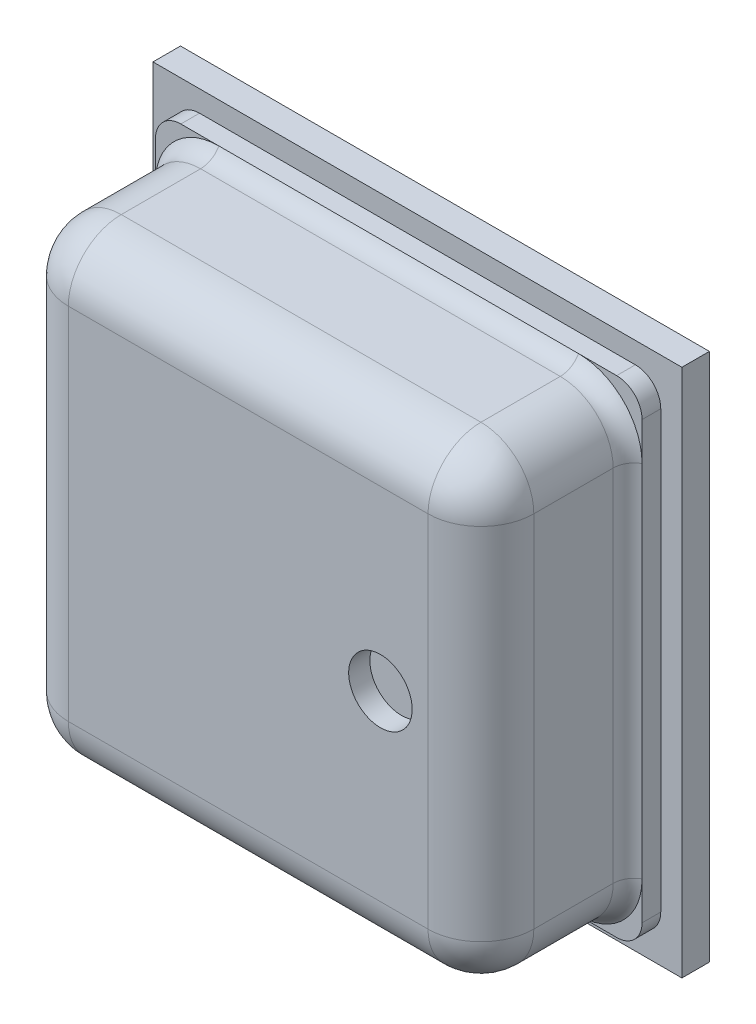
SolidWorks part; units mm, degrees
ref_plane "Спереди" through (0, 0, 0) normal (0, 0, 1) x (1, 0, 0)
ref_plane "Сверху" through (0, 0, 0) normal (0, 1, 0) x (1, 0, 0)
ref_plane "Справа" through (0, 0, 0) normal (1, 0, 0) x (0, 0, -1)
other "Configuration Table"
sketch "Эскиз1" plane through (0, 0, 0) normal (0, 1, 0) x (1, 0, 0)
  line L0 (58.2389, -66.049) -> (296.1934, -66.049) construction
  line L1 (0, 0) -> (0, -0.93) construction
  line L2 (-1.25, 0) -> (1.25, 0)
  line L3 (-1.25, 0) -> (-1.25, -0.13)
  line L4 (-1.25, -0.13) -> (1.25, -0.13)
  line L5 (1.25, 0) -> (1.25, -0.13)
  line L6 (0, -0.88) -> (-0.85, -0.88) construction
  line L7 (-1.2, -0.305) -> (-1.2, -0.155) construction
  line L8 (-1.05, -0.68) -> (-1.05, -0.305) construction
  line L9 (0, -0.83) -> (-0.85, -0.83)
  line L10 (-1, -0.68) -> (-1, -0.305)
  line L11 (0, -0.93) -> (-0.85, -0.93)
  line L12 (-1.1, -0.68) -> (-1.1, -0.305)
  line L13 (0, -0.83) -> (0, -0.93)
  line L14 (-1.2, -0.105) -> (-1.2, -0.205)
  line L15 (-1.15, -0.2184) -> (-1.15, -0.13)
  line L16 (1.15, -0.2184) -> (1.15, -0.13)
  line L17 (1.1, -0.68) -> (1.1, -0.305)
  line L18 (1, -0.68) -> (1, -0.305)
  line L19 (0, -0.93) -> (0.85, -0.93)
  line L20 (0, -0.83) -> (0.85, -0.83)
  arc A0 (-1.05, -0.305) -> (-1.2, -0.155) centre (-1.2, -0.305) ccw construction
  arc A1 (-0.85, -0.88) -> (-1.05, -0.68) centre (-0.85, -0.68) cw construction
  arc A2 (-0.85, -0.83) -> (-1, -0.68) centre (-0.85, -0.68) cw
  arc A3 (-1, -0.305) -> (-1.2, -0.105) centre (-1.2, -0.305) ccw
  arc A4 (-0.85, -0.93) -> (-1.1, -0.68) centre (-0.85, -0.68) cw
  arc A5 (-1.1, -0.305) -> (-1.2, -0.205) centre (-1.2, -0.305) ccw
  arc A6 (1.1, -0.305) -> (1.2, -0.205) centre (1.2, -0.305) cw
  arc A7 (1, -0.305) -> (1.2, -0.105) centre (1.2, -0.305) cw
  arc A8 (0.85, -0.83) -> (1, -0.68) centre (0.85, -0.68) ccw
  arc A9 (0.85, -0.93) -> (1.1, -0.68) centre (0.85, -0.68) ccw
  dimension "D4" = 1.05
  dimension "D6" = 0.2
  dimension "D7" = 0.15
  dimension "D1" = 2.5
  dimension "D2" = 0.13
  dimension "D3" = 0.93
  dimension "D5" = 0.05
  dimension "D8" = 0.025
  dimension "D11" = 2.3
  dimension "D9" = 0.05
  dimension "D10" = 0.05
extrude "Бобышка-Вытянуть1" add sketch "Эскиз1" along normal mid plane 2.5 contours A3 L4 L5 L2 L3 L14 | L4 A3 L14 region at (0.0059, 0, 0.0647) region at (-1.1634, 0, 0.1199)
extrude "Бобышка-Вытянуть2" add sketch "Эскиз1<3>" along normal mid plane 2.5 separate body contours A5 L12 A4 L11 L13 L9 A2 L10 A3 L4 L15 | L19 A9 L17 A6 L16 L4 A7 L18 A8 L20 L13 region at (1.136, 0, 0.1742) region at (-1.1266, 0, 0.144)
sketch "Эскиз1<3>" plane through (0, 0, 0) normal (0, 1, 0) x (1, 0, 0) same geometry as "Эскиз1"
pattern_circular "Круговой массив1" count 2 every 90 about axis through (0, 0, 0) along (0, 0, 1) of bodies 104
sketch "Эскиз2" plane through (0, 0, 0.13) normal (0, 0, 1) x (1, 0, 0)
  line L0 (-0.85, 1.25) -> (-0.85, -1.25) construction
  line L1 (-0.85, 0.85) -> (-1.25, 0.85)
  line L2 (-0.85, 0.85) -> (-0.85, 1.25)
  line L3 (-0.85, 1.25) -> (-1.25, 1.25)
  line L4 (-1.25, 0.85) -> (-1.25, 1.25)
  line L5 (1.25, 0.85) -> (-1.25, 0.85) construction
  line L6 (0.85, 1.25) -> (0.85, -1.25) construction
  line L7 (0.85, 0.85) -> (1.25, 0.85)
  line L8 (0.85, 0.85) -> (0.85, 1.25)
  line L9 (0.85, 1.25) -> (1.25, 1.25)
  line L10 (1.25, 0.85) -> (1.25, 1.25)
  line L11 (1.25, -0.85) -> (-1.25, -0.85) construction
  line L12 (-0.85, -0.85) -> (-1.25, -0.85)
  line L13 (-0.85, -0.85) -> (-0.85, -1.25)
  line L14 (-0.85, -1.25) -> (-1.25, -1.25)
  line L15 (-1.25, -0.85) -> (-1.25, -1.25)
  line L17 (0.85, -0.85) -> (1.25, -0.85)
  line L18 (0.85, -0.85) -> (0.85, -1.25)
  line L19 (0.85, -1.25) -> (1.25, -1.25)
  line L20 (1.25, -0.85) -> (1.25, -1.25)
  point P26 (-1.2667, -1.2667)
  point P27 (-1.25, -1.25)
extrude "Вырез-Вытянуть1" cut sketch "Эскиз2" along normal through all
sketch "Эскиз3" plane through (0, -0.85, 0) normal (0, -1, 0) x (1, 0, 0)
  line L10 (0.85, 0.93) -> (0.85, 0.83)
  line L11 (1, 0.68) -> (1, 0.305)
  line L12 (1.1032, 0.13) -> (1.15, 0.13)
  line L13 (1.15, 0.13) -> (1.15, 0.2184)
  line L14 (1.1, 0.305) -> (1.1, 0.68)
  line L15 (0.85, 0.93) -> (0.85, 0.83)
  line L16 (1, 0.68) -> (1, 0.305)
  line L17 (1.1032, 0.13) -> (1.15, 0.13)
  line L18 (1.15, 0.13) -> (1.15, 0.2184)
  line L19 (1.1, 0.305) -> (1.1, 0.68)
  line L21 (-1.25, 0.93) -> (1.25, 0.93)
  line L22 (-1.25, 0.93) -> (-1.25, 0.83)
  line L23 (-1.25, 0.83) -> (1.25, 0.83)
  line L24 (1.25, 0.93) -> (1.25, 0.83)
  line L25 (-0.85, 0.83) -> (-0.85, 0.93)
  line L26 (-1.1, 0.68) -> (-1.1, 0.305)
  line L27 (-1.15, 0.2184) -> (-1.15, 0.13)
  line L28 (-1.15, 0.13) -> (-1.1032, 0.13)
  line L29 (-1, 0.305) -> (-1, 0.68)
  line L30 (-0.85, 0.83) -> (-0.85, 0.93)
  line L31 (-1.1, 0.68) -> (-1.1, 0.305)
  line L32 (-1.15, 0.2184) -> (-1.15, 0.13)
  line L33 (-1.15, 0.13) -> (-1.1032, 0.13)
  line L34 (-1, 0.305) -> (-1, 0.68)
  arc A8 (1.1, 0.68) -> (0.85, 0.93) centre (0.85, 0.68) ccw
  arc A9 (1, 0.68) -> (0.85, 0.83) centre (0.85, 0.68) ccw
  arc A10 (1, 0.305) -> (1.1032, 0.13) centre (1.2, 0.305) ccw
  arc A11 (1.1, 0.305) -> (1.15, 0.2184) centre (1.2, 0.305) ccw
  arc A12 (1.1, 0.68) -> (0.85, 0.93) centre (0.85, 0.68) ccw
  arc A13 (1, 0.68) -> (0.85, 0.83) centre (0.85, 0.68) ccw
  arc A14 (1, 0.305) -> (1.1032, 0.13) centre (1.2, 0.305) ccw
  arc A15 (1.1, 0.305) -> (1.15, 0.2184) centre (1.2, 0.305) ccw
  arc A20 (-0.85, 0.83) -> (-1, 0.68) centre (-0.85, 0.68) ccw
  arc A21 (-0.85, 0.93) -> (-1.1, 0.68) centre (-0.85, 0.68) ccw
  arc A22 (-1.15, 0.2184) -> (-1.1, 0.305) centre (-1.2, 0.305) ccw
  arc A23 (-1.1032, 0.13) -> (-1, 0.305) centre (-1.2, 0.305) ccw
  arc A24 (-0.85, 0.83) -> (-1, 0.68) centre (-0.85, 0.68) ccw
  arc A25 (-0.85, 0.93) -> (-1.1, 0.68) centre (-0.85, 0.68) ccw
  arc A26 (-1.15, 0.2184) -> (-1.1, 0.305) centre (-1.2, 0.305) ccw
  arc A27 (-1.1032, 0.13) -> (-1, 0.305) centre (-1.2, 0.305) ccw
  line M20 (1.25, 0.83) -> (1.25, 0.93)
  line M21 (1.25, 0.93) -> (0.85, 0.93)
  dimension "D1" = 0
  dimension "D2" = 0
extrude "Вырез-Вытянуть2" cut sketch "Эскиз3" against normal through all contours A25 L21 L22 L23 | A12 L23 M20 M21 region at (1.1158, -0.85, 0.885) region at (-1.1158, -0.85, 0.885)
sketch "Эскиз4" plane through (0.85, 0, 0) normal (1, 0, 0) x (0, 0, -1)
  line L10 (-0.68, 1) -> (-0.305, 1)
  line L11 (-0.13, 1.1032) -> (-0.13, 1.15)
  line L12 (-0.13, 1.15) -> (-0.2184, 1.15)
  line L13 (-0.305, 1.1) -> (-0.68, 1.1)
  line L14 (-0.93, 0.85) -> (-0.83, 0.85)
  line L15 (-0.68, 1) -> (-0.305, 1)
  line L16 (-0.13, 1.1032) -> (-0.13, 1.15)
  line L17 (-0.13, 1.15) -> (-0.2184, 1.15)
  line L18 (-0.305, 1.1) -> (-0.68, 1.1)
  line L19 (-0.93, 0.85) -> (-0.83, 0.85)
  line L21 (-0.93, -1.25) -> (-0.83, -1.25)
  line L22 (-0.93, -1.25) -> (-0.93, 1.25)
  line L23 (-0.93, 1.25) -> (-0.83, 1.25)
  line L24 (-0.83, -1.25) -> (-0.83, 1.25)
  line L25 (-0.68, -1.1) -> (-0.305, -1.1)
  line L26 (-0.2184, -1.15) -> (-0.13, -1.15)
  line L27 (-0.13, -1.15) -> (-0.13, -1.1032)
  line L28 (-0.305, -1) -> (-0.68, -1)
  line L29 (-0.83, -0.85) -> (-0.93, -0.85)
  line L30 (-0.68, -1.1) -> (-0.305, -1.1)
  line L31 (-0.2184, -1.15) -> (-0.13, -1.15)
  line L32 (-0.13, -1.15) -> (-0.13, -1.1032)
  line L33 (-0.305, -1) -> (-0.68, -1)
  line L34 (-0.83, -0.85) -> (-0.93, -0.85)
  arc A8 (-0.68, 1) -> (-0.83, 0.85) centre (-0.68, 0.85) ccw
  arc A9 (-0.305, 1) -> (-0.13, 1.1032) centre (-0.305, 1.2) ccw
  arc A10 (-0.305, 1.1) -> (-0.2184, 1.15) centre (-0.305, 1.2) ccw
  arc A11 (-0.68, 1.1) -> (-0.93, 0.85) centre (-0.68, 0.85) ccw
  arc A12 (-0.68, 1) -> (-0.83, 0.85) centre (-0.68, 0.85) ccw
  arc A13 (-0.305, 1) -> (-0.13, 1.1032) centre (-0.305, 1.2) ccw
  arc A14 (-0.305, 1.1) -> (-0.2184, 1.15) centre (-0.305, 1.2) ccw
  arc A15 (-0.68, 1.1) -> (-0.93, 0.85) centre (-0.68, 0.85) ccw
  arc A20 (-0.93, -0.85) -> (-0.68, -1.1) centre (-0.68, -0.85) ccw
  arc A21 (-0.2184, -1.15) -> (-0.305, -1.1) centre (-0.305, -1.2) ccw
  arc A22 (-0.13, -1.1032) -> (-0.305, -1) centre (-0.305, -1.2) ccw
  arc A23 (-0.83, -0.85) -> (-0.68, -1) centre (-0.68, -0.85) ccw
  arc A24 (-0.93, -0.85) -> (-0.68, -1.1) centre (-0.68, -0.85) ccw
  arc A25 (-0.2184, -1.15) -> (-0.305, -1.1) centre (-0.305, -1.2) ccw
  arc A26 (-0.13, -1.1032) -> (-0.305, -1) centre (-0.305, -1.2) ccw
  arc A27 (-0.83, -0.85) -> (-0.68, -1) centre (-0.68, -0.85) ccw
  arc M26 (-0.68, 1.1) -> (-0.93, 0.85) centre (-0.68, 0.85) ccw
  dimension "D1" = 0
  dimension "D2" = 0
extrude "Вырез-Вытянуть3" cut sketch "Эскиз4" against normal through all contours A24 L22 L21 L24 | L24 L23 L22 M26 region at (0.85, 1.1158, 0.885) region at (0.85, -1.1158, 0.885)
sketch "Эскиз5" plane through (0.85, 0, 0) normal (1, 0, 0) x (0, 0, -1)
  line L10 (-0.68, 1) -> (-0.305, 1)
  line L11 (-0.13, 1.1032) -> (-0.13, 1.15)
  line L12 (-0.13, 1.15) -> (-0.2184, 1.15)
  line L13 (-0.305, 1.1) -> (-0.68, 1.1)
  line L14 (-0.93, 0.85) -> (-0.83, 0.85)
  line L15 (-0.68, 1) -> (-0.305, 1)
  line L16 (-0.13, 1.1032) -> (-0.13, 1.15)
  line L17 (-0.13, 1.15) -> (-0.2184, 1.15)
  line L18 (-0.305, 1.1) -> (-0.68, 1.1)
  line L19 (-0.93, 0.85) -> (-0.83, 0.85)
  arc A8 (-0.68, 1) -> (-0.83, 0.85) centre (-0.68, 0.85) ccw
  arc A9 (-0.305, 1) -> (-0.13, 1.1032) centre (-0.305, 1.2) ccw
  arc A10 (-0.305, 1.1) -> (-0.2184, 1.15) centre (-0.305, 1.2) ccw
  arc A11 (-0.68, 1.1) -> (-0.93, 0.85) centre (-0.68, 0.85) ccw
  arc A12 (-0.68, 1) -> (-0.83, 0.85) centre (-0.68, 0.85) ccw
  arc A13 (-0.305, 1) -> (-0.13, 1.1032) centre (-0.305, 1.2) ccw
  arc A14 (-0.305, 1.1) -> (-0.2184, 1.15) centre (-0.305, 1.2) ccw
  arc A15 (-0.68, 1.1) -> (-0.93, 0.85) centre (-0.68, 0.85) ccw
  dimension "D1" = 0
revolve "Повернуть1" add sketch "Эскиз5" angle 90 about L19
sketch "Эскиз6" plane through (0, -0.85, 0) normal (0, -1, 0) x (1, 0, 0)
  line L10 (0.85, 0.93) -> (0.85, 0.83)
  line L11 (1, 0.68) -> (1, 0.305)
  line L12 (1.1032, 0.13) -> (1.15, 0.13)
  line L13 (1.15, 0.13) -> (1.15, 0.2184)
  line L14 (1.1, 0.305) -> (1.1, 0.68)
  line L15 (0.85, 0.93) -> (0.85, 0.83)
  line L16 (1, 0.68) -> (1, 0.305)
  line L17 (1.1032, 0.13) -> (1.15, 0.13)
  line L18 (1.15, 0.13) -> (1.15, 0.2184)
  line L19 (1.1, 0.305) -> (1.1, 0.68)
  arc A8 (1, 0.68) -> (0.85, 0.83) centre (0.85, 0.68) ccw
  arc A9 (1, 0.305) -> (1.1032, 0.13) centre (1.2, 0.305) ccw
  arc A10 (1.1, 0.305) -> (1.15, 0.2184) centre (1.2, 0.305) ccw
  arc A11 (1.1, 0.68) -> (0.85, 0.93) centre (0.85, 0.68) ccw
  arc A12 (1, 0.68) -> (0.85, 0.83) centre (0.85, 0.68) ccw
  arc A13 (1, 0.305) -> (1.1032, 0.13) centre (1.2, 0.305) ccw
  arc A14 (1.1, 0.305) -> (1.15, 0.2184) centre (1.2, 0.305) ccw
  arc A15 (1.1, 0.68) -> (0.85, 0.93) centre (0.85, 0.68) ccw
  dimension "D1" = 0
revolve "Повернуть2" add sketch "Эскиз6" angle 90 about L15
sketch "Эскиз7" plane through (-0.85, 0, 0) normal (-1, 0, 0) x (0, 0, 1)
  line L10 (0.93, -0.85) -> (0.83, -0.85)
  line L11 (0.68, -1) -> (0.305, -1)
  line L12 (0.13, -1.1032) -> (0.13, -1.15)
  line L13 (0.13, -1.15) -> (0.2184, -1.15)
  line L14 (0.305, -1.1) -> (0.68, -1.1)
  line L15 (0.93, -0.85) -> (0.83, -0.85)
  line L16 (0.68, -1) -> (0.305, -1)
  line L17 (0.13, -1.1032) -> (0.13, -1.15)
  line L18 (0.13, -1.15) -> (0.2184, -1.15)
  line L19 (0.305, -1.1) -> (0.68, -1.1)
  arc A8 (0.68, -1) -> (0.83, -0.85) centre (0.68, -0.85) ccw
  arc A9 (0.305, -1) -> (0.13, -1.1032) centre (0.305, -1.2) ccw
  arc A10 (0.305, -1.1) -> (0.2184, -1.15) centre (0.305, -1.2) ccw
  arc A11 (0.68, -1.1) -> (0.93, -0.85) centre (0.68, -0.85) ccw
  arc A12 (0.68, -1) -> (0.83, -0.85) centre (0.68, -0.85) ccw
  arc A13 (0.305, -1) -> (0.13, -1.1032) centre (0.305, -1.2) ccw
  arc A14 (0.305, -1.1) -> (0.2184, -1.15) centre (0.305, -1.2) ccw
  arc A15 (0.68, -1.1) -> (0.93, -0.85) centre (0.68, -0.85) ccw
  dimension "D1" = 0
revolve "Повернуть3" add sketch "Эскиз7" angle 90 about L15
sketch "Эскиз8" plane through (0, 0.85, 0) normal (0, 1, 0) x (1, 0, 0)
  line L10 (-0.85, -0.93) -> (-0.85, -0.83)
  line L11 (-1, -0.68) -> (-1, -0.305)
  line L12 (-1.1032, -0.13) -> (-1.15, -0.13)
  line L13 (-1.15, -0.13) -> (-1.15, -0.2184)
  line L14 (-1.1, -0.305) -> (-1.1, -0.68)
  line L15 (-0.85, -0.93) -> (-0.85, -0.83)
  line L16 (-1, -0.68) -> (-1, -0.305)
  line L17 (-1.1032, -0.13) -> (-1.15, -0.13)
  line L18 (-1.15, -0.13) -> (-1.15, -0.2184)
  line L19 (-1.1, -0.305) -> (-1.1, -0.68)
  arc A8 (-1, -0.68) -> (-0.85, -0.83) centre (-0.85, -0.68) ccw
  arc A9 (-1, -0.305) -> (-1.1032, -0.13) centre (-1.2, -0.305) ccw
  arc A10 (-1.1, -0.305) -> (-1.15, -0.2184) centre (-1.2, -0.305) ccw
  arc A11 (-1.1, -0.68) -> (-0.85, -0.93) centre (-0.85, -0.68) ccw
  arc A12 (-1, -0.68) -> (-0.85, -0.83) centre (-0.85, -0.68) ccw
  arc A13 (-1, -0.305) -> (-1.1032, -0.13) centre (-1.2, -0.305) ccw
  arc A14 (-1.1, -0.305) -> (-1.15, -0.2184) centre (-1.2, -0.305) ccw
  arc A15 (-1.1, -0.68) -> (-0.85, -0.93) centre (-0.85, -0.68) ccw
  dimension "D1" = 0
revolve "Повернуть4" add sketch "Эскиз8" angle 90 about L15
sketch "Эскиз9" plane through (0, 0, 0.13) normal (0, 0, 1) x (1, 0, 0)
  line L0 (-1.15, 0.85) -> (-1.15, -0.85) construction
  line L1 (-1.03, 1.15) -> (1.03, 1.15)
  line L2 (-1.15, 1.03) -> (-1.15, -1.03)
  line L3 (-1.03, -1.15) -> (1.03, -1.15)
  line L4 (1.15, 1.03) -> (1.15, -1.03)
  line L5 (1.15, 0.85) -> (1.15, -0.85) construction
  line L6 (0.85, -1.15) -> (-0.85, -1.15) construction
  line L7 (0.85, 1.15) -> (-0.85, 1.15) construction
  arc A2 (-0.85, 1.15) -> (-1.15, 0.85) centre (-0.85, 0.85) ccw
  arc A3 (-0.85, 1.15) -> (-1.15, 0.85) centre (-0.85, 0.85) ccw
  arc A5 (1.15, 0.85) -> (0.85, 1.15) centre (0.85, 0.85) ccw
  arc A6 (1.15, 0.85) -> (0.85, 1.15) centre (0.85, 0.85) ccw
  arc A8 (0.85, -1.15) -> (1.15, -0.85) centre (0.85, -0.85) ccw
  arc A9 (0.85, -1.15) -> (1.15, -0.85) centre (0.85, -0.85) ccw
  arc A10 (-1.03, 1.15) -> (-1.15, 1.03) centre (-1.03, 1.03) ccw
  arc A11 (-1.15, -0.85) -> (-0.85, -1.15) centre (-0.85, -0.85) ccw
  arc A12 (-1.15, -0.85) -> (-0.85, -1.15) centre (-0.85, -0.85) ccw
  arc A13 (-1.15, -1.03) -> (-1.03, -1.15) centre (-1.03, -1.03) ccw
  arc A14 (1.03, -1.15) -> (1.15, -1.03) centre (1.03, -1.03) ccw
  arc A15 (1.03, 1.15) -> (1.15, 1.03) centre (1.03, 1.03) cw
  point P26 (-1.15, 1.15)
  point P31 (1.15, -1.15)
  dimension "D5" = 0.12
  dimension "D1" = 0
  dimension "D2" = 0
  dimension "D3" = 0
  dimension "D4" = 0
extrude "Бобышка-Вытянуть3" add sketch "Эскиз9" along normal up to vertex (0.0884 mm away) contours L1 A10 L2 A3 | A15 L1 A6 L4 | L2 A13 L3 A12 | L3 A14 L4 A9 region at (-1.0753, 1.0753, 0.13) region at (1.0753, 1.0753, 0.13) region at (-1.0753, -1.0753, 0.13) region at (1.0753, -1.0753, 0.13) up to point (-1.15, 0.85, 0.2184)
sketch "Эскиз10" plane through (0, 0, 0.93) normal (0, 0, 1) x (1, 0, 0)
  line L0 (-1.25, 1.25) -> (1.25, 1.25) construction
  line L1 (1.25, 1.25) -> (1.25, -1.25) construction
  circle A0 centre (0.625, 0.012) radius 0.15
  dimension "D1" = 0.3
  dimension "D2" = 1.238
  dimension "D3" = 0.625
extrude "Вырез-Вытянуть4" cut sketch "Эскиз10" against normal up to surface (0.8 mm away) up to face at (0, 0, 0.13)
sketch "Эскиз11" plane through (0, 0, 0) normal (0, 0, -1) x (-1, 0, 0)
  line L0 (0, 0) -> (0, 1.15) construction
  line L1 (-1.15, 1.15) -> (-0.8, 1.15)
  line L2 (-1.15, 1.15) -> (-1.15, 0.8)
  line L3 (-1.15, 0.8) -> (-0.8, 0.8)
  line L4 (-0.8, 1.15) -> (-0.8, 0.8)
  line L5 (-0.5, 1.15) -> (-0.15, 1.15)
  line L6 (-0.5, 1.15) -> (-0.5, 0.8)
  line L7 (-0.5, 0.8) -> (-0.15, 0.8)
  line L8 (-0.15, 1.15) -> (-0.15, 0.8)
  line L9 (0.15, 1.15) -> (0.5, 1.15)
  line L10 (0.15, 1.15) -> (0.15, 0.8)
  line L11 (0.15, 0.8) -> (0.5, 0.8)
  line L12 (0.5, 1.15) -> (0.5, 0.8)
  line L13 (0.8, 1.15) -> (1.15, 1.15)
  line L14 (0.8, 1.15) -> (0.8, 0.8)
  line L15 (0.8, 0.8) -> (1.15, 0.8)
  line L16 (1.15, 1.15) -> (1.15, 0.8)
  line L17 (-1.15, -1.15) -> (-0.8, -1.15)
  line L18 (-1.15, -1.15) -> (-1.15, -0.8)
  line L19 (-1.15, -0.8) -> (-0.8, -0.8)
  line L20 (-0.8, -1.15) -> (-0.8, -0.8)
  line L21 (-0.5, -0.8) -> (-0.15, -0.8)
  line L22 (-0.5, -0.8) -> (-0.5, -1.15)
  line L23 (-0.5, -1.15) -> (-0.15, -1.15)
  line L24 (-0.15, -0.8) -> (-0.15, -1.15)
  line L25 (0.15, -0.8) -> (0.5, -0.8)
  line L26 (0.15, -0.8) -> (0.15, -1.15)
  line L27 (0.15, -1.15) -> (0.5, -1.15)
  line L28 (0.5, -0.8) -> (0.5, -1.15)
  line L29 (0.8, -0.8) -> (1.15, -0.8)
  line L30 (0.8, -0.8) -> (0.8, -1.15)
  line L31 (0.8, -1.15) -> (1.15, -1.15)
  line L32 (1.15, -0.8) -> (1.15, -1.15)
  line L33 (0.8, 0.8) -> (-0.8, -0.8) construction
  line L34 (-0.8, 1.15) -> (-0.5, 1.15) construction
  line L35 (-0.15, 1.15) -> (0.15, 1.15) construction
  line L36 (0.5, 1.15) -> (0.8, 1.15) construction
  line L37 (0.975, 0.8) -> (0.975, 0.5) construction
  line L38 (1.25, 1.25) -> (-1.25, 1.25) construction
  circle A0 centre (0.975, 0.5) radius 0.1
  point P32 (1.15, -0.975)
  point P33 (1.15, 0.975)
  point P43 (0.9459, 0.5329)
  dimension "D4" = 0.2
  dimension "D1" = 0.35
  dimension "D2" = 1.95
  dimension "D3" = 1.95
  dimension "D5" = 0.75
extrude "Бобышка-Вытянуть4" add sketch "Эскиз11" along normal blind 0.015 separate body
